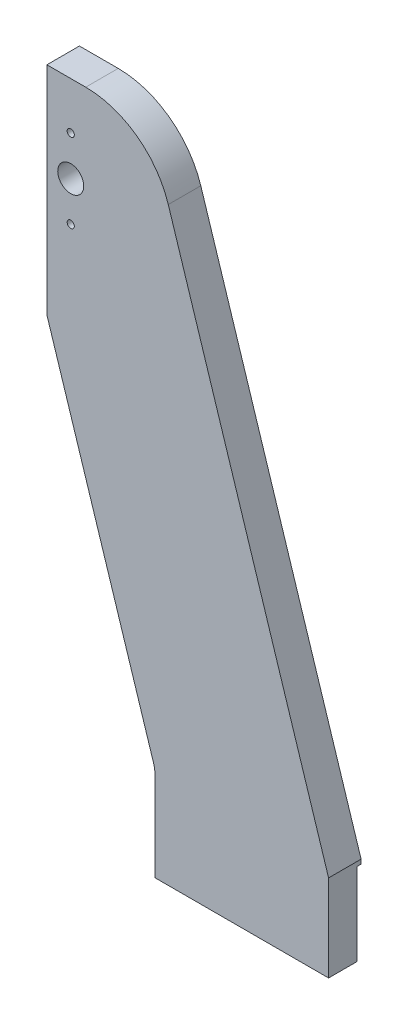
SolidWorks part; units mm, degrees
material "3.3547 (EN-AW 5083)"
ref_plane "Alzado" through (0, 0, 0) normal (0, 0, 1) x (1, 0, 0)
ref_plane "Planta" through (0, 0, 0) normal (0, 1, 0) x (1, 0, 0)
ref_plane "Vista lateral" through (0, 0, 0) normal (1, 0, 0) x (0, 0, -1)
sketch "Croquis1" plane through (0, 0, 0) normal (0, 0, 1) x (1, 0, 0)
  line L0 (80, 0) -> (80, 40)
  line L1 (-50, 300) -> (-32.095, 300)
  line L2 (-50, 300) -> (-50, 200)
  line L3 (0, 0) -> (80, 0)
  line L4 (6.0164, 272.1459) -> (80, 40)
  line L9 (-50, 200) -> (-0.9443, 46.0729)
  line L11 (0, 40) -> (0, 0)
  arc A2 (6.0164, 272.1459) -> (-32.095, 300) centre (-32.095, 260) ccw
  arc A3 (0, 40) -> (-0.9443, 46.0729) centre (-20, 40) ccw
  point P14 (0, 43.1099)
  dimension "D7" = 20
  dimension "D9" = 40
  dimension "D1" = 40
  dimension "D2" = 300
  dimension "D3" = 80
  dimension "D4" = 50
  dimension "D5" = 100
  dimension "D6" = 40
extrude "Saliente-Extruir1" add sketch "Croquis1" along normal blind 15
sketch "Croquis2" plane through (0, 0, 0) normal (0, 0, -1) x (-1, 0, 0)
  line L0 (32.095, 300) -> (50, 300) construction
  line L2 (50, 300) -> (50, 200) construction
  circle A0 centre (39, 260) radius 6
  dimension "D3" = 12
  dimension "D1" = 40
  dimension "D2" = 11
extrude "Cortar-Extruir1" cut sketch "Croquis2" against normal through all
hole_wizard "Perforador para roscar para macho de roscar para M44" positions "Croquis7" profile "Croquis8" hole size "M4" standard "DIN"
sketch "Croquis7" plane through (0, 0, 15) normal (0, 0, 1) x (1, 0, 0)
  line L0 (-39, 278.25) -> (-39, 241.75)
  circle A0 centre (-39, 260) radius 6 construction
  point P1 (-39, 278.25)
  point P2 (-39, 241.75)
  dimension "D1" = 18.25
  dimension "D2" = 18.25
sketch "Croquis8" plane through (-39, 278.25, 15) normal (1, 0, 0) x (0, -1, 0)
  line L0 (0, 0) -> (0, 7.9914)
  line L1 (0, 7.9914) -> (1.65, 7)
  line L2 (1.65, 7) -> (1.65, 0)
  line L5 (1.65, 0) -> (0, 0)
  line L10 (0, 7.9914) -> (-1.65, 7) construction
  line L11 (0, -6.35) -> (0, 107.95) construction
  dimension "Diámetro de taladro" = 3.3
  dimension "Profundidad de taladro" = 7
  dimension "Ángulo de perforador" = 118
sketch "Croquis9" plane through (0, 0, 0) normal (0, 0, -1) x (-1, 0, 0)
  line L1 (0, 0) -> (-80, 0)
  line L2 (0, 0) -> (0, 38)
  line L3 (0, 38) -> (-80, 38)
  line L4 (-80, 0) -> (-80, 38)
  dimension "D1" = 80
  dimension "D2" = 38
extrude "Cortar-Extruir2" cut sketch "Croquis9" against normal blind 2
hole_wizard "Perforador para roscar para macho de roscar para M45" positions "Croquis10" profile "Croquis11" hole size "M4" standard "DIN"
sketch "Croquis10" plane through (-50, 0, 0) normal (-1, 0, 0) x (0, 0, 1)
  line L0 (15, 300) -> (0, 300) construction
  line L1 (15, 300) -> (15, 200) construction
  point P0 (9, 285)
  point P2 (9, 235)
  dimension "D1" = 15
  dimension "D2" = 65
  dimension "D3" = 6
  dimension "D4" = 6
sketch "Croquis11" plane through (-50, 285, 9) normal (0, 1, 0) x (0, 0, 1)
  line L0 (0, 0) -> (0, 15.9914)
  line L1 (0, 15.9914) -> (1.65, 15)
  line L2 (1.65, 15) -> (1.65, 0)
  line L5 (1.65, 0) -> (0, 0)
  line L10 (0, 15.9914) -> (-1.65, 15) construction
  line L11 (0, -6.35) -> (0, 107.95) construction
  dimension "Diámetro de taladro" = 3.3
  dimension "Profundidad de taladro" = 15
  dimension "Ángulo de perforador" = 118
hole_wizard "Taladros de espiga de Ø4.0mm1" positions "Croquis12" profile "Croquis13" hole size "Ø4.0" standard "DIN"
sketch "Croquis12" plane through (-50, 0, 0) normal (-1, 0, 0) x (0, 0, 1)
  line L0 (15, 300) -> (0, 300) construction
  line L1 (15, 300) -> (15, 200) construction
  point P0 (9, 274)
  point P2 (9, 246)
  dimension "D1" = 26
  dimension "D2" = 54
  dimension "D3" = 6
  dimension "D4" = 6
sketch "Croquis13" plane through (-50, 274, 9) normal (0, 1, 0) x (0, 0, 1)
  line L0 (0, 0) -> (0, 18.2017)
  line L1 (0, 18.2017) -> (2, 17)
  line L2 (2, 17) -> (2, 0)
  line L5 (2, 0) -> (0, 0)
  line L10 (0, 18.2017) -> (-2, 17) construction
  line L11 (0, -6.35) -> (0, 107.95) construction
  dimension "Diámetro de taladro" = 4
  dimension "Profundidad de taladro" = 17
  dimension "Ángulo de perforador" = 118
